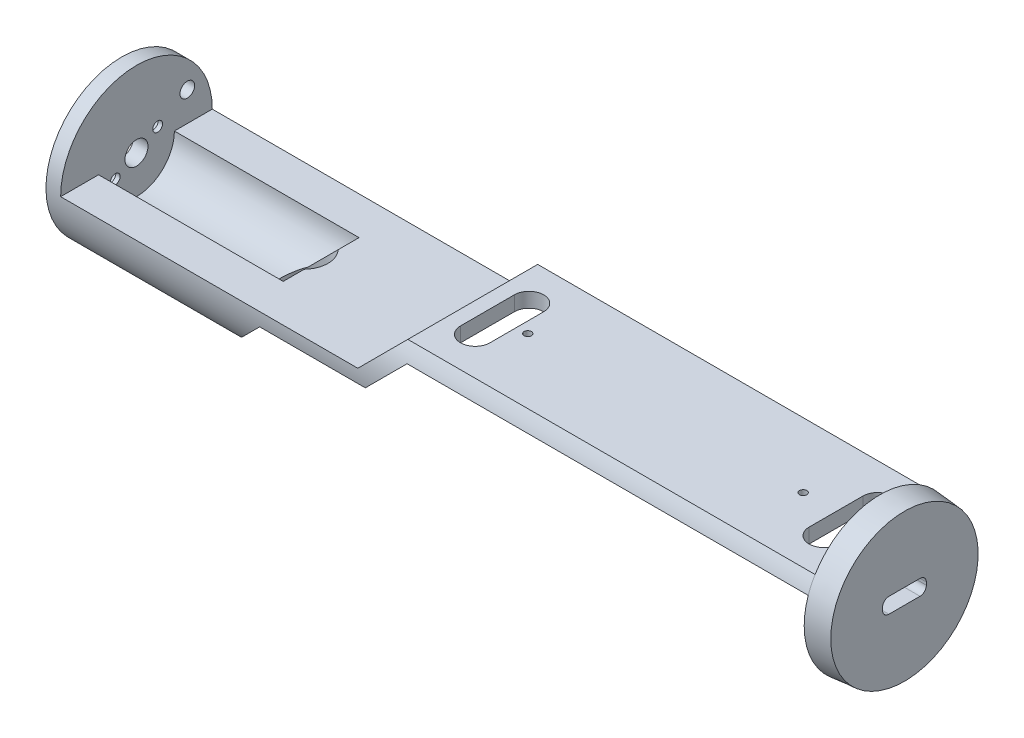
SolidWorks part; units mm, degrees
ref_plane "Front Plane" through (0, 0, 0) normal (0, 0, 1) x (1, 0, 0)
ref_plane "Top Plane" through (0, 0, 0) normal (0, 1, 0) x (1, 0, 0)
ref_plane "Right Plane" through (0, 0, 0) normal (1, 0, 0) x (0, 0, -1)
sketch "Sketch2" plane through (0, 0, 0) normal (1, 0, 0) x (0, 0, -1)
  circle A0 centre (0, 0) radius 15.5
  dimension "D1" = 31
extrude "Boss-Extrude1" add sketch "Sketch2" along normal blind 160
sketch "Sketch6" plane through (0, 0, 0) normal (0, 0, 1) x (1, 0, 0)
  line L0 (3, 15.5) -> (3, 0)
  line L1 (160, 15.5) -> (0, 15.5) construction
  line L2 (3, 0) -> (63.75, 0)
  line L4 (3, 15.5) -> (83, 15.5)
  line L5 (0, 15.5) -> (0, -15.5) construction
  line L7 (63.75, 0) -> (71.75, 8)
  line L8 (71.75, 8) -> (155, 8)
  line L10 (155, 8) -> (155, 15.5)
  line L11 (155, 15.5) -> (83, 15.5)
  line L12 (160, -15.5) -> (160, 15.5) construction
  dimension "D1" = 3
  dimension "D2" = 5
  dimension "D3" = 8
  dimension "D4" = 45
  dimension "D5" = 60.75
extrude "Cut-Extrude1" cut sketch "Sketch6" against normal through all both and the other way through all
sketch "Sketch7" plane through (0, 0, 0) normal (1, 0, 0) x (0, 0, -1)
  circle A0 centre (0, 0) radius 7.75
  dimension "D1" = 15.5
extrude "Cut-Extrude2" cut sketch "Sketch7" along normal blind 30 from surface contours A0 starting at face at (3, 7.75, 0)
chamfer "Chamfer1" distance 7.75 angle 45 1 edges at (33, 0, 0)
sketch "Sketch8" plane through (0, 0, 0) normal (0, 0, 1) x (1, 0, 0)
  line L0 (0, -10.75) -> (35.6458, -10.75)
  line L1 (0, 15.5) -> (0, -15.5) construction
  line L2 (35.6458, -10.75) -> (43.3958, -3)
  line L3 (43.3958, -3) -> (64.9926, -3)
  line L4 (3, 0) -> (63.75, 0) construction
  line L5 (3, -7.75) -> (33, -7.75) construction
  line L6 (160, -15.5) -> (160, 15.5) construction
  line L7 (155, 8) -> (71.75, 8) construction
  line L9 (0, -15.5) -> (160, -15.5) construction
  line L10 (155, -15.5) -> (0, -15.5)
  line L11 (0, -15.5) -> (0, -10.75)
  line L12 (64.9926, -3) -> (72.9926, 5)
  line L13 (72.9926, 5) -> (155, 5)
  line L15 (155, 5) -> (155, -15.5)
  line L17 (63.75, 0) -> (71.75, 8) construction
  dimension "D1" = 45
  dimension "D2" = 3
  dimension "D3" = 3
  dimension "D4" = 4
  dimension "D5" = 3
  dimension "D6" = 3
  dimension "D8" = 5
extrude "Cut-Extrude3" cut sketch "Sketch8" against normal through all both and the other way through all
sketch "Sketch9" plane through (0, 0, 0) normal (1, 0, 0) x (0, 0, -1)
  line L0 (8.9523, 5.1686) -> (-8.9523, -5.1686) construction
  line L1 (13.0769, 0) -> (-13.0769, 0) construction
  line L2 (-4.7371, 8.2049) -> (4.7371, -8.2049) construction
  circle A0 centre (4.3301, 2.5) radius 1
  circle A1 centre (-4.3301, -2.5) radius 1
  circle A2 centre (4.3301, 2.5) radius 1.9
  circle A3 centre (-4.3301, -2.5) radius 1.9
  circle A4 centre (0, 0) radius 2.35
  circle A5 centre (0, 0) radius 5 construction
  point P4 (0, 0)
  point P7 (0, 0)
  point P14 (0, 0)
  point P15 (0, 0)
  dimension "D3" = 2
  dimension "D4" = 3.8
  dimension "D2" = 10
  dimension "D5" = 4.7
  dimension "D1" = 30
extrude "Cut-Extrude4" cut sketch "Sketch9" along normal blind 10 contours A1 | A0 | A4 region at (0, 2.5, -4.3301) region at (0, -2.5, 4.3301) region at (0, 0, 0)
extrude "Cut-Extrude5" cut sketch "Sketch9<3>" along normal blind 2.1 contours A2 A0 | A3 A1 region at (0, 2.5, -2.4839) region at (0, -2.5, 6.1764)
sketch "Sketch9<3>" plane through (0, 0, 0) normal (1, 0, 0) x (0, 0, -1) same geometry as "Sketch9"
sketch "Sketch11" plane through (0, 0, 0) normal (1, 0, 0) x (0, 0, -1)
  line L0 (0, 0) -> (0, 22.0661) construction
  line L5 (-3.175, 1.58) -> (3.175, 1.58)
  line L6 (-4.475, 0.28) -> (-4.475, -0.28)
  line L7 (-3.175, -1.58) -> (3.175, -1.58)
  line L8 (4.475, 0.28) -> (4.475, -0.28)
  line L9 (-4.475, 1.58) -> (4.475, -1.58) construction
  line L10 (-4.475, -1.58) -> (4.475, 1.58) construction
  arc A2 (-4.475, -0.28) -> (-3.175, -1.58) centre (-3.175, -0.28) ccw
  arc A3 (3.175, -1.58) -> (4.475, -0.28) centre (3.175, -0.28) ccw
  arc A4 (3.175, 1.58) -> (4.475, 0.28) centre (3.175, 0.28) cw
  arc A5 (-3.175, 1.58) -> (-4.475, 0.28) centre (-3.175, 0.28) ccw
  point P3 (0, 0)
  dimension "D2" = 3.16
  dimension "D4" = 1.3
  dimension "D1" = 8.95
extrude "Cut-Extrude6" cut sketch "Sketch11" along normal blind 10 from surface starting at face at (155, 11.75, 0)
sketch "Sketch12" plane through (0, 0, 0) normal (0, 0, 1) x (1, 0, 0)
  line L2 (160, -15.5) -> (160, 15.5) construction
  line L3 (160, -15.5) -> (160, 15.5) construction
  line L5 (160, 15.5) -> (155, 15.5)
  line L6 (0, 0) -> (177.1073, 0) construction
  line L8 (155, 15.5) -> (160, 15.0626)
  line L9 (160, 15.0626) -> (160, 15.5)
  dimension "D1" = 5
revolve "Cut-Revolve1" cut sketch "Sketch12" angle 360 about L6
sketch "Sketch13" plane through (0, 0, 0) normal (1, 0, 0) x (0, 0, -1)
  line L0 (13.0348, 7.5256) -> (-13.0348, -7.5256) construction
  line L1 (9.9747, 0) -> (-9.9747, 0) construction
  circle A0 centre (10.3923, 6) radius 1.5
  circle A1 centre (-10.3923, -6) radius 1.5
  circle A2 centre (0, 0) radius 12 construction
  point P5 (0, 0)
  point P9 (0, 0)
  dimension "D2" = 3
  dimension "D3" = 24
  dimension "D1" = 30
extrude "Cut-Extrude7" cut sketch "Sketch13" along normal blind 10
cosmetic thread "Cosmetic Thread1" parameters "D1"=3, "D2"=4
cosmetic thread "Cosmetic Thread2" parameters "D1"=8, "D2"=4
sketch "Sketch14" plane through (0, 0, 0) normal (0, 1, 0) x (1, 0, 0)
  line L0 (0, 0) -> (183.562, 0) construction
  line L1 (72.9926, 14.6714) -> (72.9926, -14.6714) construction
  circle A0 centre (82.9926, 0) radius 0.75
  circle A1 centre (139.2926, 0) radius 0.75
  dimension "D1" = 1.5
  dimension "D2" = 56.3
  dimension "D3" = 10
extrude "Cut-Extrude8" cut sketch "Sketch14" along normal through all
sketch "Sketch16" plane through (0, 0, 0) normal (0, 1, 0) x (1, 0, 0)
  circle A0 centre (37.14, 0) radius 5
  dimension "D2" = 10
  dimension "D1" = 37.14
extrude "Cut-Extrude9" cut sketch "Sketch16" against normal blind 16
sketch "Sketch19" plane through (0, 0, 0) normal (0, 1, 0) x (1, 0, 0)
  line L0 (77.75, 5.5) -> (77.75, -5.5) construction
  line L1 (80.75, 5.5) -> (80.75, -5.5)
  line L2 (74.75, 5.5) -> (74.75, -5.5)
  line L3 (149, 5.5) -> (149, -5.5) construction
  line L4 (152, 5.5) -> (152, -5.5)
  line L5 (146, 5.5) -> (146, -5.5)
  line L6 (71.75, 13.2759) -> (71.75, -13.2759) construction
  line L7 (155, 13.2759) -> (155, -13.2759) construction
  arc A0 (80.75, 5.5) -> (74.75, 5.5) centre (77.75, 5.5) ccw
  arc A1 (74.75, -5.5) -> (80.75, -5.5) centre (77.75, -5.5) ccw
  arc A2 (152, 5.5) -> (146, 5.5) centre (149, 5.5) ccw
  arc A3 (146, -5.5) -> (152, -5.5) centre (149, -5.5) ccw
  point P2 (77.75, 0)
  point P7 (149, 0)
  dimension "D3" = 3
  dimension "D1" = 6
  dimension "D2" = 6
  dimension "D4" = 11
extrude "Cut-Extrude12" cut sketch "Sketch19" along normal blind 16
